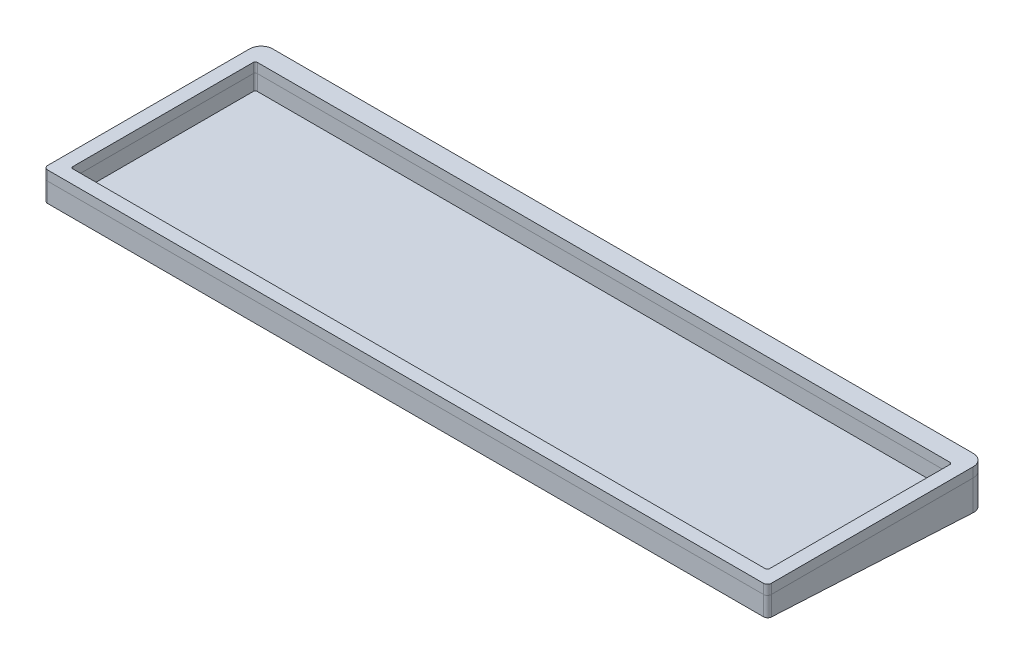
SolidWorks part; units mm, degrees
ref_plane "Front Plane" through (0, 0, 0) normal (0, 0, 1) x (1, 0, 0)
ref_plane "Top Plane" through (0, 0, 0) normal (0, 1, 0) x (1, 0, 0)
ref_plane "Right Plane" through (0, 0, 0) normal (1, 0, 0) x (0, 0, -1)
sketch "Sketch1" plane through (0, 0, 0) normal (0, 1, 0) x (1, 0, 0)
  line L1 (-178.825, 47.625) -> (178.825, 47.625)
  line L2 (-179.825, 46.625) -> (-179.825, -46.625)
  line L3 (-178.825, -47.625) -> (178.825, -47.625)
  line L4 (179.825, 46.625) -> (179.825, -46.625)
  line L5 (-179.825, 47.625) -> (179.825, -47.625) construction
  line L6 (-179.825, -47.625) -> (179.825, 47.625) construction
  arc A0 (178.825, -47.625) -> (179.825, -46.625) centre (178.825, -46.625) ccw
  arc A1 (178.825, 47.625) -> (179.825, 46.625) centre (178.825, 46.625) cw
  arc A2 (-179.825, -46.625) -> (-178.825, -47.625) centre (-178.825, -46.625) ccw
  arc A3 (-178.825, 47.625) -> (-179.825, 46.625) centre (-178.825, 46.625) ccw
  circle A4 centre (157.075, 19.175) radius 1.1
  circle A5 centre (136.925, -16.775) radius 1.1
  circle A6 centre (-153.475, 33.725) radius 1.1
  circle A7 centre (17.925, 22.275) radius 1.1
  circle A8 centre (17.875, -35.075) radius 1.1
  circle A9 centre (-130.375, -35.725) radius 1.1
  point P0 (0, 0)
  dimension "D3" = 1
  dimension "D4" = 2.2
  dimension "D7" = 2.2
  dimension "D8" = 2.2
  dimension "D9" = 2.2
  dimension "D10" = 2.2
  dimension "D11" = 2.2
  dimension "D1" = 359.65
  dimension "D2" = 95.25
  dimension "D5" = 22.75
  dimension "D6" = 28.45
  dimension "D12" = 42.9
  dimension "D13" = 30.85
  dimension "D14" = 25.35
  dimension "D15" = 161.9
  dimension "D16" = 12.55
  dimension "D17" = 161.95
  dimension "D18" = 11.9
  dimension "D19" = 49.45
  dimension "D20" = 13.9
  dimension "D21" = 26.35
sketch "Sketch2" plane through (0, 0, 0) normal (0, 1, 0) x (1, 0, 0)
  line L0 (-179.825, 46.625) -> (-179.825, -46.625) construction
  line L1 (-178.825, -47.625) -> (178.825, -47.625) construction
  line L2 (179.825, 46.625) -> (179.825, -46.625) construction
  line L3 (-178.825, 47.625) -> (178.825, 47.625) construction
  line L4 (-179.825, 46.625) -> (-179.825, -46.625)
  line L5 (-178.825, -47.625) -> (178.825, -47.625)
  line L6 (179.825, 46.625) -> (179.825, -46.625)
  line L7 (-178.825, 47.625) -> (178.825, 47.625)
  line L9 (-180.825, 57.625) -> (180.825, 57.625)
  line L10 (-186.825, 51.625) -> (-186.825, -52.625)
  line L11 (-184.825, -54.625) -> (184.825, -54.625)
  line L12 (186.825, 51.625) -> (186.825, -52.625)
  circle A0 centre (157.075, 19.175) radius 1.1 construction
  circle A1 centre (136.925, -16.775) radius 1.1 construction
  circle A2 centre (17.875, -35.075) radius 1.1 construction
  circle A3 centre (17.925, 22.275) radius 1.1 construction
  circle A4 centre (-153.475, 33.725) radius 1.1 construction
  circle A5 centre (-130.375, -35.725) radius 1.1 construction
  arc A6 (-179.825, -46.625) -> (-178.825, -47.625) centre (-178.825, -46.625) ccw construction
  arc A7 (178.825, -47.625) -> (179.825, -46.625) centre (178.825, -46.625) ccw construction
  arc A8 (179.825, 46.625) -> (178.825, 47.625) centre (178.825, 46.625) ccw construction
  arc A9 (-178.825, 47.625) -> (-179.825, 46.625) centre (-178.825, 46.625) ccw construction
  circle A10 centre (157.075, 19.175) radius 1.1
  circle A11 centre (136.925, -16.775) radius 1.1
  circle A12 centre (17.875, -35.075) radius 1.1
  circle A13 centre (17.925, 22.275) radius 1.1
  circle A14 centre (-153.475, 33.725) radius 1.1
  circle A15 centre (-130.375, -35.725) radius 1.1
  arc A16 (-179.825, -46.625) -> (-178.825, -47.625) centre (-178.825, -46.625) ccw
  arc A17 (178.825, -47.625) -> (179.825, -46.625) centre (178.825, -46.625) ccw
  arc A18 (179.825, 46.625) -> (178.825, 47.625) centre (178.825, 46.625) ccw
  arc A19 (-178.825, 47.625) -> (-179.825, 46.625) centre (-178.825, 46.625) ccw
  arc A20 (180.825, 57.625) -> (186.825, 51.625) centre (180.825, 51.625) cw
  arc A21 (-180.825, 57.625) -> (-186.825, 51.625) centre (-180.825, 51.625) ccw
  arc A22 (184.825, -54.625) -> (186.825, -52.625) centre (184.825, -52.625) ccw
  arc A23 (-186.825, -52.625) -> (-184.825, -54.625) centre (-184.825, -52.625) ccw
  point P30 (0, 0)
  dimension "D5" = 6
  dimension "D6" = 2
  dimension "D1" = 10
  dimension "D2" = 7
  dimension "D3" = 7
  dimension "D4" = 7
extrude "Boss-Extrude1" add sketch "Sketch2" along normal blind 13 contours L10 A23 L11 A22 L12 A20 L9 A21 A19 L7 A18 L6 A17 L5 A16 L4 region at (0, 0, -53.7235)
sketch "Sketch4" plane through (0, 0, 0) normal (0, -1, 0) x (1, 0, 0)
  line L0 (186.825, -51.625) -> (186.825, 52.625) construction
  line L1 (-180.825, -57.625) -> (180.825, -57.625) construction
  line L2 (-186.825, -51.625) -> (-186.825, 52.625) construction
  line L3 (-184.825, 54.625) -> (184.825, 54.625) construction
  line L4 (-179.825, 46.625) -> (-179.825, -46.625)
  line L5 (178.825, 47.625) -> (-178.825, 47.625)
  line L6 (179.825, -46.625) -> (179.825, 46.625)
  line L7 (-178.825, -47.625) -> (178.825, -47.625)
  line L8 (-179.825, 46.625) -> (-179.825, -46.625)
  line L10 (179.825, -46.625) -> (179.825, 46.625)
  line L11 (-178.825, -47.625) -> (178.825, -47.625)
  line L12 (186.825, -51.625) -> (186.825, 52.625)
  line L13 (-180.825, -57.625) -> (180.825, -57.625)
  line L14 (-186.825, -51.625) -> (-186.825, 52.625)
  line L15 (-184.825, 54.625) -> (184.825, 54.625)
  arc A0 (186.825, 52.625) -> (184.825, 54.625) centre (184.825, 52.625) ccw construction
  arc A1 (180.825, -57.625) -> (186.825, -51.625) centre (180.825, -51.625) ccw construction
  arc A2 (-186.825, -51.625) -> (-180.825, -57.625) centre (-180.825, -51.625) ccw construction
  arc A3 (-184.825, 54.625) -> (-186.825, 52.625) centre (-184.825, 52.625) ccw construction
  arc A4 (-179.825, -46.625) -> (-178.825, -47.625) centre (-178.825, -46.625) ccw
  arc A5 (-178.825, 47.625) -> (-179.825, 46.625) centre (-178.825, 46.625) ccw
  arc A6 (179.825, 46.625) -> (178.825, 47.625) centre (178.825, 46.625) ccw
  arc A7 (178.825, -47.625) -> (179.825, -46.625) centre (178.825, -46.625) ccw
  arc A8 (-179.825, -46.625) -> (-178.825, -47.625) centre (-178.825, -46.625) ccw
  arc A9 (-178.825, 47.625) -> (-179.825, 46.625) centre (-178.825, 46.625) ccw
  arc A10 (179.825, 46.625) -> (178.825, 47.625) centre (178.825, 46.625) ccw
  arc A11 (178.825, -47.625) -> (179.825, -46.625) centre (178.825, -46.625) ccw
  arc A12 (186.825, 52.625) -> (184.825, 54.625) centre (184.825, 52.625) ccw
  arc A13 (180.825, -57.625) -> (186.825, -51.625) centre (180.825, -51.625) ccw
  arc A14 (-186.825, -51.625) -> (-180.825, -57.625) centre (-180.825, -51.625) ccw
  arc A15 (-184.825, 54.625) -> (-186.825, 52.625) centre (-184.825, 52.625) ccw
  arc M9 (-178.825, -47.625) -> (-179.825, -46.625) centre (-178.825, -46.625) cw
  line M10 (-179.825, -46.625) -> (-179.825, 46.625)
  arc M11 (-179.825, 46.625) -> (-178.825, 47.625) centre (-178.825, 46.625) cw
  line M12 (-178.825, 47.625) -> (178.825, 47.625)
  arc M13 (178.825, 47.625) -> (179.825, 46.625) centre (178.825, 46.625) cw
  line M14 (179.825, 46.625) -> (179.825, -46.625)
  arc M15 (179.825, -46.625) -> (178.825, -47.625) centre (178.825, -46.625) cw
  line M16 (178.825, -47.625) -> (-178.825, -47.625)
  line M17 (-186.825, 52.625) -> (-186.825, -51.625)
  arc M18 (-186.825, -51.625) -> (-180.825, -57.625) centre (-180.825, -51.625) ccw
  line M19 (-180.825, -57.625) -> (180.825, -57.625)
  arc M20 (180.825, -57.625) -> (186.825, -51.625) centre (180.825, -51.625) ccw
  line M21 (186.825, -51.625) -> (186.825, 52.625)
  arc M22 (186.825, 52.625) -> (184.825, 54.625) centre (184.825, 52.625) ccw
  line M23 (184.825, 54.625) -> (-184.825, 54.625)
  arc M24 (-184.825, 54.625) -> (-186.825, 52.625) centre (-184.825, 52.625) ccw
  dimension "D1" = 0
extrude "Boss-Extrude3" add sketch "Sketch4" along normal blind 10.5 contours M24 M17 M18 M19 M20 M21 M22 M23 M16 M9 M10 M11 M12 M13 M14 M15 | M9 M16 M15 M14 M13 M12 M11 M10 region at (0, 0, 0) region at (182.3089, 0, -53.1089)
sketch "Sketch8" plane through (-186.825, 0, 0) normal (-1, 0, 0) x (0, 0, 1)
  line L0 (54.625, 0) -> (-57.625, 0) construction
  line L2 (-57.625, 13) -> (-57.625, -10.5) construction
  line L4 (-57.625, -7.8828) -> (-57.625, -10.5)
  line L5 (-57.625, -10.5) -> (54.625, -10.5)
  line L11 (54.625, -2) -> (54.625, -10.5)
  line L12 (54.625, 13) -> (54.625, -10.5) construction
  line L13 (-57.625, -7.8828) -> (54.625, -2)
  point P3 (54.625, -1.946)
  point P10 (-57.625, -8.0998)
  dimension "D1" = 2
  dimension "D2" = 10.5
  dimension "D3" = 87
extrude "Cut-Extrude4" cut sketch "Sketch8" against normal blind 400
sketch "Sketch9" plane through (0, 0, 0) normal (0, 1, 0) x (1, 0, 0)
  line L0 (-121.9453, 45.1) -> (-108.9453, 45.1)
  line L1 (-121.9453, 31.1) -> (-108.9453, 31.1)
  line L2 (-122.4453, 44.6) -> (-122.4453, 31.6)
  line L3 (-108.4453, 44.6) -> (-108.4453, 31.6)
  line L4 (-102.8953, 45.1) -> (-89.8953, 45.1)
  line L5 (-102.8953, 31.1) -> (-89.8953, 31.1)
  line L6 (-103.3953, 44.6) -> (-103.3953, 31.6)
  line L7 (-89.3953, 44.6) -> (-89.3953, 31.6)
  line L8 (-83.8453, 45.1) -> (-70.8453, 45.1)
  line L9 (-83.8453, 31.1) -> (-70.8453, 31.1)
  line L10 (-84.3453, 44.6) -> (-84.3453, 31.6)
  line L11 (-70.3453, 44.6) -> (-70.3453, 31.6)
  line L12 (-64.7953, 45.1) -> (-51.7953, 45.1)
  line L13 (-64.7953, 31.1) -> (-51.7953, 31.1)
  line L14 (-65.2953, 44.6) -> (-65.2953, 31.6)
  line L15 (-51.2953, 44.6) -> (-51.2953, 31.6)
  line L16 (-45.7453, 45.1) -> (-32.7453, 45.1)
  line L17 (-45.7453, 31.1) -> (-32.7453, 31.1)
  line L18 (-46.2453, 44.6) -> (-46.2453, 31.6)
  line L19 (-32.2453, 44.6) -> (-32.2453, 31.6)
  line L20 (-26.6953, 45.1) -> (-13.6953, 45.1)
  line L21 (-26.6953, 31.1) -> (-13.6953, 31.1)
  line L22 (-27.1953, 44.6) -> (-27.1953, 31.6)
  line L23 (-13.1953, 44.6) -> (-13.1953, 31.6)
  line L24 (-7.6453, 45.1) -> (5.3547, 45.1)
  line L25 (-7.6453, 31.1) -> (5.3547, 31.1)
  line L26 (-8.1453, 44.6) -> (-8.1453, 31.6)
  line L27 (5.8547, 44.6) -> (5.8547, 31.6)
  line L28 (11.4047, 45.1) -> (24.4047, 45.1)
  line L29 (11.4047, 31.1) -> (24.4047, 31.1)
  line L30 (10.9047, 44.6) -> (10.9047, 31.6)
  line L31 (24.9047, 44.6) -> (24.9047, 31.6)
  line L32 (30.4547, 45.1) -> (43.4547, 45.1)
  line L33 (30.4547, 31.1) -> (43.4547, 31.1)
  line L34 (29.9547, 44.6) -> (29.9547, 31.6)
  line L35 (43.9547, 44.6) -> (43.9547, 31.6)
  line L36 (49.5047, 45.1) -> (62.5047, 45.1)
  line L37 (49.5047, 31.1) -> (62.5047, 31.1)
  line L38 (49.0047, 44.6) -> (49.0047, 31.6)
  line L39 (63.0047, 44.6) -> (63.0047, 31.6)
  line L40 (68.5547, 45.1) -> (81.5547, 45.1)
  line L41 (68.5547, 31.1) -> (81.5547, 31.1)
  line L42 (68.0547, 44.6) -> (68.0547, 31.6)
  line L43 (82.0547, 44.6) -> (82.0547, 31.6)
  line L44 (87.6047, 45.1) -> (100.6047, 45.1)
  line L45 (87.6047, 31.1) -> (100.6047, 31.1)
  line L46 (87.1047, 44.6) -> (87.1047, 31.6)
  line L47 (101.1047, 44.6) -> (101.1047, 31.6)
  line L48 (106.6547, 45.1) -> (119.6547, 45.1)
  line L49 (106.6547, 31.1) -> (119.6547, 31.1)
  line L50 (106.1547, 44.6) -> (106.1547, 31.6)
  line L51 (120.1547, 44.6) -> (120.1547, 31.6)
  line L52 (135.2297, 45.1) -> (148.2297, 45.1)
  line L53 (135.2297, 31.1) -> (148.2297, 31.1)
  line L54 (134.7297, 44.6) -> (134.7297, 31.6)
  line L55 (148.7297, 44.6) -> (148.7297, 31.6)
  line L56 (150.6677, 44.1) -> (156.6677, 44.1)
  line L57 (150.6677, 29.1) -> (156.6677, 29.1)
  line L58 (150.1677, 43.6) -> (150.1677, 29.6)
  line L59 (157.1677, 43.6) -> (157.1677, 29.6)
  line L60 (126.7917, 44.1) -> (132.7917, 44.1)
  line L61 (126.7917, 29.1) -> (132.7917, 29.1)
  line L62 (126.2917, 43.6) -> (126.2917, 29.6)
  line L63 (133.2917, 43.6) -> (133.2917, 29.6)
  line L64 (163.8047, 45.1) -> (176.8047, 45.1)
  line L65 (163.8047, 31.1) -> (176.8047, 31.1)
  line L66 (163.3047, 44.6) -> (163.3047, 31.6)
  line L67 (177.3047, 44.6) -> (177.3047, 31.6)
  line L68 (-117.1828, 26.05) -> (-104.1828, 26.05)
  line L69 (-117.1828, 12.05) -> (-104.1828, 12.05)
  line L70 (-117.6828, 25.55) -> (-117.6828, 12.55)
  line L71 (-103.6828, 25.55) -> (-103.6828, 12.55)
  line L72 (-93.3703, 26.05) -> (-80.3703, 26.05)
  line L73 (-93.3703, 12.05) -> (-80.3703, 12.05)
  line L74 (-93.8703, 25.55) -> (-93.8703, 12.55)
  line L75 (-79.8703, 25.55) -> (-79.8703, 12.55)
  line L76 (-74.3203, 26.05) -> (-61.3203, 26.05)
  line L77 (-74.3203, 12.05) -> (-61.3203, 12.05)
  line L78 (-74.8203, 25.55) -> (-74.8203, 12.55)
  line L79 (-60.8203, 25.55) -> (-60.8203, 12.55)
  line L80 (-55.2703, 26.05) -> (-42.2703, 26.05)
  line L81 (-55.2703, 12.05) -> (-42.2703, 12.05)
  line L82 (-55.7703, 25.55) -> (-55.7703, 12.55)
  line L83 (-41.7703, 25.55) -> (-41.7703, 12.55)
  line L84 (-36.2203, 26.05) -> (-23.2203, 26.05)
  line L85 (-36.2203, 12.05) -> (-23.2203, 12.05)
  line L86 (-36.7203, 25.55) -> (-36.7203, 12.55)
  line L87 (-22.7203, 25.55) -> (-22.7203, 12.55)
  line L88 (-17.1703, 26.05) -> (-4.1703, 26.05)
  line L89 (-17.1703, 12.05) -> (-4.1703, 12.05)
  line L90 (-17.6703, 25.55) -> (-17.6703, 12.55)
  line L91 (-3.6703, 25.55) -> (-3.6703, 12.55)
  line L92 (1.8797, 26.05) -> (14.8797, 26.05)
  line L93 (1.8797, 12.05) -> (14.8797, 12.05)
  line L94 (1.3797, 25.55) -> (1.3797, 12.55)
  line L95 (15.3797, 25.55) -> (15.3797, 12.55)
  line L96 (20.9297, 26.05) -> (33.9297, 26.05)
  line L97 (20.9297, 12.05) -> (33.9297, 12.05)
  line L98 (20.4297, 25.55) -> (20.4297, 12.55)
  line L99 (34.4297, 25.55) -> (34.4297, 12.55)
  line L100 (39.9797, 26.05) -> (52.9797, 26.05)
  line L101 (39.9797, 12.05) -> (52.9797, 12.05)
  line L102 (39.4797, 25.55) -> (39.4797, 12.55)
  line L103 (53.4797, 25.55) -> (53.4797, 12.55)
  line L104 (59.0297, 26.05) -> (72.0297, 26.05)
  line L105 (59.0297, 12.05) -> (72.0297, 12.05)
  line L106 (58.5297, 25.55) -> (58.5297, 12.55)
  line L107 (72.5297, 25.55) -> (72.5297, 12.55)
  line L108 (78.0797, 26.05) -> (91.0797, 26.05)
  line L109 (78.0797, 12.05) -> (91.0797, 12.05)
  line L110 (77.5797, 25.55) -> (77.5797, 12.55)
  line L111 (91.5797, 25.55) -> (91.5797, 12.55)
  line L112 (97.1297, 26.05) -> (110.1297, 26.05)
  line L113 (97.1297, 12.05) -> (110.1297, 12.05)
  line L114 (96.6297, 25.55) -> (96.6297, 12.55)
  line L115 (110.6297, 25.55) -> (110.6297, 12.55)
  line L116 (116.1797, 26.05) -> (129.1797, 26.05)
  line L117 (116.1797, 12.05) -> (129.1797, 12.05)
  line L118 (115.6797, 25.55) -> (115.6797, 12.55)
  line L119 (129.6797, 25.55) -> (129.6797, 12.55)
  line L120 (139.9922, 26.05) -> (152.9922, 26.05)
  line L121 (139.9922, 12.05) -> (152.9922, 12.05)
  line L122 (139.4922, 25.55) -> (139.4922, 12.55)
  line L123 (153.4922, 25.55) -> (153.4922, 12.55)
  line L124 (163.8047, 26.05) -> (176.8047, 26.05)
  line L125 (163.8047, 12.05) -> (176.8047, 12.05)
  line L126 (163.3047, 25.55) -> (163.3047, 12.55)
  line L127 (177.3047, 25.55) -> (177.3047, 12.55)
  line L128 (-114.8016, 7) -> (-101.8016, 7)
  line L129 (-114.8016, -7) -> (-101.8016, -7)
  line L130 (-115.3016, 6.5) -> (-115.3016, -6.5)
  line L131 (-101.3016, 6.5) -> (-101.3016, -6.5)
  line L132 (-88.6078, 7) -> (-75.6078, 7)
  line L133 (-88.6078, -7) -> (-75.6078, -7)
  line L134 (-89.1078, 6.5) -> (-89.1078, -6.5)
  line L135 (-75.1078, 6.5) -> (-75.1078, -6.5)
  line L136 (-69.5578, 7) -> (-56.5578, 7)
  line L137 (-69.5578, -7) -> (-56.5578, -7)
  line L138 (-70.0578, 6.5) -> (-70.0578, -6.5)
  line L139 (-56.0578, 6.5) -> (-56.0578, -6.5)
  line L140 (-50.5078, 7) -> (-37.5078, 7)
  line L141 (-50.5078, -7) -> (-37.5078, -7)
  line L142 (-51.0078, 6.5) -> (-51.0078, -6.5)
  line L143 (-37.0078, 6.5) -> (-37.0078, -6.5)
  line L144 (-31.4578, 7) -> (-18.4578, 7)
  line L145 (-31.4578, -7) -> (-18.4578, -7)
  line L146 (-31.9578, 6.5) -> (-31.9578, -6.5)
  line L147 (-17.9578, 6.5) -> (-17.9578, -6.5)
  line L148 (-12.4078, 7) -> (0.5922, 7)
  line L149 (-12.4078, -7) -> (0.5922, -7)
  line L150 (-12.9078, 6.5) -> (-12.9078, -6.5)
  line L151 (1.0922, 6.5) -> (1.0922, -6.5)
  line L152 (6.6422, 7) -> (19.6422, 7)
  line L153 (6.6422, -7) -> (19.6422, -7)
  line L154 (6.1422, 6.5) -> (6.1422, -6.5)
  line L155 (20.1422, 6.5) -> (20.1422, -6.5)
  line L156 (25.6922, 7) -> (38.6922, 7)
  line L157 (25.6922, -7) -> (38.6922, -7)
  line L158 (25.1922, 6.5) -> (25.1922, -6.5)
  line L159 (39.1922, 6.5) -> (39.1922, -6.5)
  line L160 (44.7422, 7) -> (57.7422, 7)
  line L161 (44.7422, -7) -> (57.7422, -7)
  line L162 (44.2422, 6.5) -> (44.2422, -6.5)
  line L163 (58.2422, 6.5) -> (58.2422, -6.5)
  line L164 (63.7922, 7) -> (76.7922, 7)
  line L165 (63.7922, -7) -> (76.7922, -7)
  line L166 (63.2922, 6.5) -> (63.2922, -6.5)
  line L167 (77.2922, 6.5) -> (77.2922, -6.5)
  line L168 (82.8422, 7) -> (95.8422, 7)
  line L169 (82.8422, -7) -> (95.8422, -7)
  line L170 (82.3422, 6.5) -> (82.3422, -6.5)
  line L171 (96.3422, 6.5) -> (96.3422, -6.5)
  line L172 (101.8922, 7) -> (114.8922, 7)
  line L173 (101.8922, -7) -> (114.8922, -7)
  line L174 (101.3922, 6.5) -> (101.3922, -6.5)
  line L175 (115.3922, 6.5) -> (115.3922, -6.5)
  line L176 (132.8484, 7) -> (145.8484, 7)
  line L177 (132.8484, -7) -> (145.8484, -7)
  line L178 (132.3484, 6.5) -> (132.3484, -6.5)
  line L179 (146.3484, 6.5) -> (146.3484, -6.5)
  line L180 (148.2864, 6) -> (154.2864, 6)
  line L181 (148.2864, -9) -> (154.2864, -9)
  line L182 (147.7864, 5.5) -> (147.7864, -8.5)
  line L183 (154.7864, 5.5) -> (154.7864, -8.5)
  line L184 (124.4104, 6) -> (130.4104, 6)
  line L185 (124.4104, -9) -> (130.4104, -9)
  line L186 (123.9104, 5.5) -> (123.9104, -8.5)
  line L187 (130.9104, 5.5) -> (130.9104, -8.5)
  line L188 (163.8047, 7) -> (176.8047, 7)
  line L189 (163.8047, -7) -> (176.8047, -7)
  line L190 (163.3047, 6.5) -> (163.3047, -6.5)
  line L191 (177.3047, 6.5) -> (177.3047, -6.5)
  line L192 (-110.0391, -12.05) -> (-97.0391, -12.05)
  line L193 (-110.0391, -26.05) -> (-97.0391, -26.05)
  line L194 (-110.5391, -12.55) -> (-110.5391, -25.55)
  line L195 (-96.5391, -12.55) -> (-96.5391, -25.55)
  line L196 (-94.6011, -13.05) -> (-88.6011, -13.05)
  line L197 (-94.6011, -28.05) -> (-88.6011, -28.05)
  line L198 (-95.1011, -13.55) -> (-95.1011, -27.55)
  line L199 (-88.1011, -13.55) -> (-88.1011, -27.55)
  line L200 (-118.4771, -13.05) -> (-112.4771, -13.05)
  line L201 (-118.4771, -28.05) -> (-112.4771, -28.05)
  line L202 (-118.9771, -13.55) -> (-118.9771, -27.55)
  line L203 (-111.9771, -13.55) -> (-111.9771, -27.55)
  line L204 (-79.0828, -12.05) -> (-66.0828, -12.05)
  line L205 (-79.0828, -26.05) -> (-66.0828, -26.05)
  line L206 (-79.5828, -12.55) -> (-79.5828, -25.55)
  line L207 (-65.5828, -12.55) -> (-65.5828, -25.55)
  line L208 (-60.0328, -12.05) -> (-47.0328, -12.05)
  line L209 (-60.0328, -26.05) -> (-47.0328, -26.05)
  line L210 (-60.5328, -12.55) -> (-60.5328, -25.55)
  line L211 (-46.5328, -12.55) -> (-46.5328, -25.55)
  line L212 (-40.9828, -12.05) -> (-27.9828, -12.05)
  line L213 (-40.9828, -26.05) -> (-27.9828, -26.05)
  line L214 (-41.4828, -12.55) -> (-41.4828, -25.55)
  line L215 (-27.4828, -12.55) -> (-27.4828, -25.55)
  line L216 (-21.9328, -12.05) -> (-8.9328, -12.05)
  line L217 (-21.9328, -26.05) -> (-8.9328, -26.05)
  line L218 (-22.4328, -12.55) -> (-22.4328, -25.55)
  line L219 (-8.4328, -12.55) -> (-8.4328, -25.55)
  line L220 (-2.8828, -12.05) -> (10.1172, -12.05)
  line L221 (-2.8828, -26.05) -> (10.1172, -26.05)
  line L222 (-3.3828, -12.55) -> (-3.3828, -25.55)
  line L223 (10.6172, -12.55) -> (10.6172, -25.55)
  line L224 (16.1672, -12.05) -> (29.1672, -12.05)
  line L225 (16.1672, -26.05) -> (29.1672, -26.05)
  line L226 (15.6672, -12.55) -> (15.6672, -25.55)
  line L227 (29.6672, -12.55) -> (29.6672, -25.55)
  line L228 (35.2172, -12.05) -> (48.2172, -12.05)
  line L229 (35.2172, -26.05) -> (48.2172, -26.05)
  line L230 (34.7172, -12.55) -> (34.7172, -25.55)
  line L231 (48.7172, -12.55) -> (48.7172, -25.55)
  line L232 (54.2672, -12.05) -> (67.2672, -12.05)
  line L233 (54.2672, -26.05) -> (67.2672, -26.05)
  line L234 (53.7672, -12.55) -> (53.7672, -25.55)
  line L235 (67.7672, -12.55) -> (67.7672, -25.55)
  line L236 (73.3172, -12.05) -> (86.3172, -12.05)
  line L237 (73.3172, -26.05) -> (86.3172, -26.05)
  line L238 (72.8172, -12.55) -> (72.8172, -25.55)
  line L239 (86.8172, -12.55) -> (86.8172, -25.55)
  line L240 (92.3672, -12.05) -> (105.3672, -12.05)
  line L241 (92.3672, -26.05) -> (105.3672, -26.05)
  line L242 (91.8672, -12.55) -> (91.8672, -25.55)
  line L243 (105.8672, -12.55) -> (105.8672, -25.55)
  line L244 (118.5609, -12.05) -> (131.5609, -12.05)
  line L245 (118.5609, -26.05) -> (131.5609, -26.05)
  line L246 (118.0609, -12.55) -> (118.0609, -25.55)
  line L247 (132.0609, -12.55) -> (132.0609, -25.55)
  line L248 (144.7547, -12.05) -> (157.7547, -12.05)
  line L249 (144.7547, -26.05) -> (157.7547, -26.05)
  line L250 (144.2547, -12.55) -> (144.2547, -25.55)
  line L251 (158.2547, -12.55) -> (158.2547, -25.55)
  line L252 (163.8047, -12.05) -> (176.8047, -12.05)
  line L253 (163.8047, -26.05) -> (176.8047, -26.05)
  line L254 (163.3047, -12.55) -> (163.3047, -25.55)
  line L255 (177.3047, -12.55) -> (177.3047, -25.55)
  line L256 (-119.5641, -31.1) -> (-106.5641, -31.1)
  line L257 (-119.5641, -45.1) -> (-106.5641, -45.1)
  line L258 (-120.0641, -31.6) -> (-120.0641, -44.6)
  line L259 (-106.0641, -31.6) -> (-106.0641, -44.6)
  line L260 (-95.7516, -31.1) -> (-82.7516, -31.1)
  line L261 (-95.7516, -45.1) -> (-82.7516, -45.1)
  line L262 (-96.2516, -31.6) -> (-96.2516, -44.6)
  line L263 (-82.2516, -31.6) -> (-82.2516, -44.6)
  line L264 (-71.9391, -31.1) -> (-58.9391, -31.1)
  line L265 (-71.9391, -45.1) -> (-58.9391, -45.1)
  line L266 (-72.4391, -31.6) -> (-72.4391, -44.6)
  line L267 (-58.4391, -31.6) -> (-58.4391, -44.6)
  line L268 (-0.5016, -31.1) -> (12.4984, -31.1)
  line L269 (-0.5016, -45.1) -> (12.4984, -45.1)
  line L270 (-1.0016, -31.6) -> (-1.0016, -44.6)
  line L271 (12.9984, -31.6) -> (12.9984, -44.6)
  line L272 (52.9984, -32.1) -> (58.9984, -32.1)
  line L273 (52.9984, -47.1) -> (58.9984, -47.1)
  line L274 (52.4984, -32.6) -> (52.4984, -46.6)
  line L275 (59.4984, -32.6) -> (59.4984, -46.6)
  line L276 (-47.0016, -32.1) -> (-41.0016, -32.1)
  line L277 (-47.0016, -47.1) -> (-41.0016, -47.1)
  line L278 (-47.5016, -32.6) -> (-47.5016, -46.6)
  line L279 (-40.5016, -32.6) -> (-40.5016, -46.6)
  line L280 (68.5547, -31.1) -> (81.5547, -31.1)
  line L281 (68.5547, -45.1) -> (81.5547, -45.1)
  line L282 (68.0547, -31.6) -> (68.0547, -44.6)
  line L283 (82.0547, -31.6) -> (82.0547, -44.6)
  line L284 (87.6047, -31.1) -> (100.6047, -31.1)
  line L285 (87.6047, -45.1) -> (100.6047, -45.1)
  line L286 (87.1047, -31.6) -> (87.1047, -44.6)
  line L287 (101.1047, -31.6) -> (101.1047, -44.6)
  line L288 (106.6547, -31.1) -> (119.6547, -31.1)
  line L289 (106.6547, -45.1) -> (119.6547, -45.1)
  line L290 (106.1547, -31.6) -> (106.1547, -44.6)
  line L291 (120.1547, -31.6) -> (120.1547, -44.6)
  line L292 (125.7047, -31.1) -> (138.7047, -31.1)
  line L293 (125.7047, -45.1) -> (138.7047, -45.1)
  line L294 (125.2047, -31.6) -> (125.2047, -44.6)
  line L295 (139.2047, -31.6) -> (139.2047, -44.6)
  line L296 (144.7547, -31.1) -> (157.7547, -31.1)
  line L297 (144.7547, -45.1) -> (157.7547, -45.1)
  line L298 (144.2547, -31.6) -> (144.2547, -44.6)
  line L299 (158.2547, -31.6) -> (158.2547, -44.6)
  line L300 (163.8047, -31.1) -> (176.8047, -31.1)
  line L301 (163.8047, -45.1) -> (176.8047, -45.1)
  line L302 (163.3047, -31.6) -> (163.3047, -44.6)
  line L303 (177.3047, -31.6) -> (177.3047, -44.6)
  line L304 (-124.9703, 47.625) -> (179.8297, 47.625)
  line L305 (-124.9703, -47.625) -> (179.8297, -47.625)
  line L306 (-124.9703, 47.625) -> (-124.9703, -47.625)
  line L307 (179.8297, 47.625) -> (179.8297, -47.625)
  arc A0 (-121.9453, 45.1) -> (-122.4453, 44.6) centre (-121.9453, 44.6) ccw
  arc A1 (-108.4453, 44.6) -> (-108.9453, 45.1) centre (-108.9453, 44.6) ccw
  arc A2 (-122.4453, 31.6) -> (-121.9453, 31.1) centre (-121.9453, 31.6) ccw
  arc A3 (-108.9453, 31.1) -> (-108.4453, 31.6) centre (-108.9453, 31.6) ccw
  arc A4 (-102.8953, 45.1) -> (-103.3953, 44.6) centre (-102.8953, 44.6) ccw
  arc A5 (-89.3953, 44.6) -> (-89.8953, 45.1) centre (-89.8953, 44.6) ccw
  arc A6 (-103.3953, 31.6) -> (-102.8953, 31.1) centre (-102.8953, 31.6) ccw
  arc A7 (-89.8953, 31.1) -> (-89.3953, 31.6) centre (-89.8953, 31.6) ccw
  arc A8 (-83.8453, 45.1) -> (-84.3453, 44.6) centre (-83.8453, 44.6) ccw
  arc A9 (-70.3453, 44.6) -> (-70.8453, 45.1) centre (-70.8453, 44.6) ccw
  arc A10 (-84.3453, 31.6) -> (-83.8453, 31.1) centre (-83.8453, 31.6) ccw
  arc A11 (-70.8453, 31.1) -> (-70.3453, 31.6) centre (-70.8453, 31.6) ccw
  arc A12 (-64.7953, 45.1) -> (-65.2953, 44.6) centre (-64.7953, 44.6) ccw
  arc A13 (-51.2953, 44.6) -> (-51.7953, 45.1) centre (-51.7953, 44.6) ccw
  arc A14 (-65.2953, 31.6) -> (-64.7953, 31.1) centre (-64.7953, 31.6) ccw
  arc A15 (-51.7953, 31.1) -> (-51.2953, 31.6) centre (-51.7953, 31.6) ccw
  arc A16 (-45.7453, 45.1) -> (-46.2453, 44.6) centre (-45.7453, 44.6) ccw
  arc A17 (-32.2453, 44.6) -> (-32.7453, 45.1) centre (-32.7453, 44.6) ccw
  arc A18 (-46.2453, 31.6) -> (-45.7453, 31.1) centre (-45.7453, 31.6) ccw
  arc A19 (-32.7453, 31.1) -> (-32.2453, 31.6) centre (-32.7453, 31.6) ccw
  arc A20 (-26.6953, 45.1) -> (-27.1953, 44.6) centre (-26.6953, 44.6) ccw
  arc A21 (-13.1953, 44.6) -> (-13.6953, 45.1) centre (-13.6953, 44.6) ccw
  arc A22 (-27.1953, 31.6) -> (-26.6953, 31.1) centre (-26.6953, 31.6) ccw
  arc A23 (-13.6953, 31.1) -> (-13.1953, 31.6) centre (-13.6953, 31.6) ccw
  arc A24 (-7.6453, 45.1) -> (-8.1453, 44.6) centre (-7.6453, 44.6) ccw
  arc A25 (5.8547, 44.6) -> (5.3547, 45.1) centre (5.3547, 44.6) ccw
  arc A26 (-8.1453, 31.6) -> (-7.6453, 31.1) centre (-7.6453, 31.6) ccw
  arc A27 (5.3547, 31.1) -> (5.8547, 31.6) centre (5.3547, 31.6) ccw
  arc A28 (11.4047, 45.1) -> (10.9047, 44.6) centre (11.4047, 44.6) ccw
  arc A29 (24.9047, 44.6) -> (24.4047, 45.1) centre (24.4047, 44.6) ccw
  arc A30 (10.9047, 31.6) -> (11.4047, 31.1) centre (11.4047, 31.6) ccw
  arc A31 (24.4047, 31.1) -> (24.9047, 31.6) centre (24.4047, 31.6) ccw
  arc A32 (30.4547, 45.1) -> (29.9547, 44.6) centre (30.4547, 44.6) ccw
  arc A33 (43.9547, 44.6) -> (43.4547, 45.1) centre (43.4547, 44.6) ccw
  arc A34 (29.9547, 31.6) -> (30.4547, 31.1) centre (30.4547, 31.6) ccw
  arc A35 (43.4547, 31.1) -> (43.9547, 31.6) centre (43.4547, 31.6) ccw
  arc A36 (49.5047, 45.1) -> (49.0047, 44.6) centre (49.5047, 44.6) ccw
  arc A37 (63.0047, 44.6) -> (62.5047, 45.1) centre (62.5047, 44.6) ccw
  arc A38 (49.0047, 31.6) -> (49.5047, 31.1) centre (49.5047, 31.6) ccw
  arc A39 (62.5047, 31.1) -> (63.0047, 31.6) centre (62.5047, 31.6) ccw
  arc A40 (68.5547, 45.1) -> (68.0547, 44.6) centre (68.5547, 44.6) ccw
  arc A41 (82.0547, 44.6) -> (81.5547, 45.1) centre (81.5547, 44.6) ccw
  arc A42 (68.0547, 31.6) -> (68.5547, 31.1) centre (68.5547, 31.6) ccw
  arc A43 (81.5547, 31.1) -> (82.0547, 31.6) centre (81.5547, 31.6) ccw
  arc A44 (87.6047, 45.1) -> (87.1047, 44.6) centre (87.6047, 44.6) ccw
  arc A45 (101.1047, 44.6) -> (100.6047, 45.1) centre (100.6047, 44.6) ccw
  arc A46 (87.1047, 31.6) -> (87.6047, 31.1) centre (87.6047, 31.6) ccw
  arc A47 (100.6047, 31.1) -> (101.1047, 31.6) centre (100.6047, 31.6) ccw
  arc A48 (106.6547, 45.1) -> (106.1547, 44.6) centre (106.6547, 44.6) ccw
  arc A49 (120.1547, 44.6) -> (119.6547, 45.1) centre (119.6547, 44.6) ccw
  arc A50 (106.1547, 31.6) -> (106.6547, 31.1) centre (106.6547, 31.6) ccw
  arc A51 (119.6547, 31.1) -> (120.1547, 31.6) centre (119.6547, 31.6) ccw
  arc A52 (135.2297, 45.1) -> (134.7297, 44.6) centre (135.2297, 44.6) ccw
  arc A53 (148.7297, 44.6) -> (148.2297, 45.1) centre (148.2297, 44.6) ccw
  arc A54 (134.7297, 31.6) -> (135.2297, 31.1) centre (135.2297, 31.6) ccw
  arc A55 (148.2297, 31.1) -> (148.7297, 31.6) centre (148.2297, 31.6) ccw
  arc A56 (150.6677, 44.1) -> (150.1677, 43.6) centre (150.6677, 43.6) ccw
  arc A57 (157.1677, 43.6) -> (156.6677, 44.1) centre (156.6677, 43.6) ccw
  arc A58 (150.1677, 29.6) -> (150.6677, 29.1) centre (150.6677, 29.6) ccw
  arc A59 (156.6677, 29.1) -> (157.1677, 29.6) centre (156.6677, 29.6) ccw
  arc A60 (126.7917, 44.1) -> (126.2917, 43.6) centre (126.7917, 43.6) ccw
  arc A61 (133.2917, 43.6) -> (132.7917, 44.1) centre (132.7917, 43.6) ccw
  arc A62 (126.2917, 29.6) -> (126.7917, 29.1) centre (126.7917, 29.6) ccw
  arc A63 (132.7917, 29.1) -> (133.2917, 29.6) centre (132.7917, 29.6) ccw
  arc A64 (163.8047, 45.1) -> (163.3047, 44.6) centre (163.8047, 44.6) ccw
  arc A65 (177.3047, 44.6) -> (176.8047, 45.1) centre (176.8047, 44.6) ccw
  arc A66 (163.3047, 31.6) -> (163.8047, 31.1) centre (163.8047, 31.6) ccw
  arc A67 (176.8047, 31.1) -> (177.3047, 31.6) centre (176.8047, 31.6) ccw
  arc A68 (-117.1828, 26.05) -> (-117.6828, 25.55) centre (-117.1828, 25.55) ccw
  arc A69 (-103.6828, 25.55) -> (-104.1828, 26.05) centre (-104.1828, 25.55) ccw
  arc A70 (-117.6828, 12.55) -> (-117.1828, 12.05) centre (-117.1828, 12.55) ccw
  arc A71 (-104.1828, 12.05) -> (-103.6828, 12.55) centre (-104.1828, 12.55) ccw
  arc A72 (-93.3703, 26.05) -> (-93.8703, 25.55) centre (-93.3703, 25.55) ccw
  arc A73 (-79.8703, 25.55) -> (-80.3703, 26.05) centre (-80.3703, 25.55) ccw
  arc A74 (-93.8703, 12.55) -> (-93.3703, 12.05) centre (-93.3703, 12.55) ccw
  arc A75 (-80.3703, 12.05) -> (-79.8703, 12.55) centre (-80.3703, 12.55) ccw
  arc A76 (-74.3203, 26.05) -> (-74.8203, 25.55) centre (-74.3203, 25.55) ccw
  arc A77 (-60.8203, 25.55) -> (-61.3203, 26.05) centre (-61.3203, 25.55) ccw
  arc A78 (-74.8203, 12.55) -> (-74.3203, 12.05) centre (-74.3203, 12.55) ccw
  arc A79 (-61.3203, 12.05) -> (-60.8203, 12.55) centre (-61.3203, 12.55) ccw
  arc A80 (-55.2703, 26.05) -> (-55.7703, 25.55) centre (-55.2703, 25.55) ccw
  arc A81 (-41.7703, 25.55) -> (-42.2703, 26.05) centre (-42.2703, 25.55) ccw
  arc A82 (-55.7703, 12.55) -> (-55.2703, 12.05) centre (-55.2703, 12.55) ccw
  arc A83 (-42.2703, 12.05) -> (-41.7703, 12.55) centre (-42.2703, 12.55) ccw
  arc A84 (-36.2203, 26.05) -> (-36.7203, 25.55) centre (-36.2203, 25.55) ccw
  arc A85 (-22.7203, 25.55) -> (-23.2203, 26.05) centre (-23.2203, 25.55) ccw
  arc A86 (-36.7203, 12.55) -> (-36.2203, 12.05) centre (-36.2203, 12.55) ccw
  arc A87 (-23.2203, 12.05) -> (-22.7203, 12.55) centre (-23.2203, 12.55) ccw
  arc A88 (-17.1703, 26.05) -> (-17.6703, 25.55) centre (-17.1703, 25.55) ccw
  arc A89 (-3.6703, 25.55) -> (-4.1703, 26.05) centre (-4.1703, 25.55) ccw
  arc A90 (-17.6703, 12.55) -> (-17.1703, 12.05) centre (-17.1703, 12.55) ccw
  arc A91 (-4.1703, 12.05) -> (-3.6703, 12.55) centre (-4.1703, 12.55) ccw
  arc A92 (1.8797, 26.05) -> (1.3797, 25.55) centre (1.8797, 25.55) ccw
  arc A93 (15.3797, 25.55) -> (14.8797, 26.05) centre (14.8797, 25.55) ccw
  arc A94 (1.3797, 12.55) -> (1.8797, 12.05) centre (1.8797, 12.55) ccw
  arc A95 (14.8797, 12.05) -> (15.3797, 12.55) centre (14.8797, 12.55) ccw
  arc A96 (20.9297, 26.05) -> (20.4297, 25.55) centre (20.9297, 25.55) ccw
  arc A97 (34.4297, 25.55) -> (33.9297, 26.05) centre (33.9297, 25.55) ccw
  arc A98 (20.4297, 12.55) -> (20.9297, 12.05) centre (20.9297, 12.55) ccw
  arc A99 (33.9297, 12.05) -> (34.4297, 12.55) centre (33.9297, 12.55) ccw
  arc A100 (39.9797, 26.05) -> (39.4797, 25.55) centre (39.9797, 25.55) ccw
  arc A101 (53.4797, 25.55) -> (52.9797, 26.05) centre (52.9797, 25.55) ccw
  arc A102 (39.4797, 12.55) -> (39.9797, 12.05) centre (39.9797, 12.55) ccw
  arc A103 (52.9797, 12.05) -> (53.4797, 12.55) centre (52.9797, 12.55) ccw
  arc A104 (59.0297, 26.05) -> (58.5297, 25.55) centre (59.0297, 25.55) ccw
  arc A105 (72.5297, 25.55) -> (72.0297, 26.05) centre (72.0297, 25.55) ccw
  arc A106 (58.5297, 12.55) -> (59.0297, 12.05) centre (59.0297, 12.55) ccw
  arc A107 (72.0297, 12.05) -> (72.5297, 12.55) centre (72.0297, 12.55) ccw
  arc A108 (78.0797, 26.05) -> (77.5797, 25.55) centre (78.0797, 25.55) ccw
  arc A109 (91.5797, 25.55) -> (91.0797, 26.05) centre (91.0797, 25.55) ccw
  arc A110 (77.5797, 12.55) -> (78.0797, 12.05) centre (78.0797, 12.55) ccw
  arc A111 (91.0797, 12.05) -> (91.5797, 12.55) centre (91.0797, 12.55) ccw
  arc A112 (97.1297, 26.05) -> (96.6297, 25.55) centre (97.1297, 25.55) ccw
  arc A113 (110.6297, 25.55) -> (110.1297, 26.05) centre (110.1297, 25.55) ccw
  arc A114 (96.6297, 12.55) -> (97.1297, 12.05) centre (97.1297, 12.55) ccw
  arc A115 (110.1297, 12.05) -> (110.6297, 12.55) centre (110.1297, 12.55) ccw
  arc A116 (116.1797, 26.05) -> (115.6797, 25.55) centre (116.1797, 25.55) ccw
  arc A117 (129.6797, 25.55) -> (129.1797, 26.05) centre (129.1797, 25.55) ccw
  arc A118 (115.6797, 12.55) -> (116.1797, 12.05) centre (116.1797, 12.55) ccw
  arc A119 (129.1797, 12.05) -> (129.6797, 12.55) centre (129.1797, 12.55) ccw
  arc A120 (139.9922, 26.05) -> (139.4922, 25.55) centre (139.9922, 25.55) ccw
  arc A121 (153.4922, 25.55) -> (152.9922, 26.05) centre (152.9922, 25.55) ccw
  arc A122 (139.4922, 12.55) -> (139.9922, 12.05) centre (139.9922, 12.55) ccw
  arc A123 (152.9922, 12.05) -> (153.4922, 12.55) centre (152.9922, 12.55) ccw
  arc A124 (163.8047, 26.05) -> (163.3047, 25.55) centre (163.8047, 25.55) ccw
  arc A125 (177.3047, 25.55) -> (176.8047, 26.05) centre (176.8047, 25.55) ccw
  arc A126 (163.3047, 12.55) -> (163.8047, 12.05) centre (163.8047, 12.55) ccw
  arc A127 (176.8047, 12.05) -> (177.3047, 12.55) centre (176.8047, 12.55) ccw
  arc A128 (-114.8016, 7) -> (-115.3016, 6.5) centre (-114.8016, 6.5) ccw
  arc A129 (-101.3016, 6.5) -> (-101.8016, 7) centre (-101.8016, 6.5) ccw
  arc A130 (-115.3016, -6.5) -> (-114.8016, -7) centre (-114.8016, -6.5) ccw
  arc A131 (-101.8016, -7) -> (-101.3016, -6.5) centre (-101.8016, -6.5) ccw
  arc A132 (-88.6078, 7) -> (-89.1078, 6.5) centre (-88.6078, 6.5) ccw
  arc A133 (-75.1078, 6.5) -> (-75.6078, 7) centre (-75.6078, 6.5) ccw
  arc A134 (-89.1078, -6.5) -> (-88.6078, -7) centre (-88.6078, -6.5) ccw
  arc A135 (-75.6078, -7) -> (-75.1078, -6.5) centre (-75.6078, -6.5) ccw
  arc A136 (-69.5578, 7) -> (-70.0578, 6.5) centre (-69.5578, 6.5) ccw
  arc A137 (-56.0578, 6.5) -> (-56.5578, 7) centre (-56.5578, 6.5) ccw
  arc A138 (-70.0578, -6.5) -> (-69.5578, -7) centre (-69.5578, -6.5) ccw
  arc A139 (-56.5578, -7) -> (-56.0578, -6.5) centre (-56.5578, -6.5) ccw
  arc A140 (-50.5078, 7) -> (-51.0078, 6.5) centre (-50.5078, 6.5) ccw
  arc A141 (-37.0078, 6.5) -> (-37.5078, 7) centre (-37.5078, 6.5) ccw
  arc A142 (-51.0078, -6.5) -> (-50.5078, -7) centre (-50.5078, -6.5) ccw
  arc A143 (-37.5078, -7) -> (-37.0078, -6.5) centre (-37.5078, -6.5) ccw
  arc A144 (-31.4578, 7) -> (-31.9578, 6.5) centre (-31.4578, 6.5) ccw
  arc A145 (-17.9578, 6.5) -> (-18.4578, 7) centre (-18.4578, 6.5) ccw
  arc A146 (-31.9578, -6.5) -> (-31.4578, -7) centre (-31.4578, -6.5) ccw
  arc A147 (-18.4578, -7) -> (-17.9578, -6.5) centre (-18.4578, -6.5) ccw
  arc A148 (-12.4078, 7) -> (-12.9078, 6.5) centre (-12.4078, 6.5) ccw
  arc A149 (1.0922, 6.5) -> (0.5922, 7) centre (0.5922, 6.5) ccw
  arc A150 (-12.9078, -6.5) -> (-12.4078, -7) centre (-12.4078, -6.5) ccw
  arc A151 (0.5922, -7) -> (1.0922, -6.5) centre (0.5922, -6.5) ccw
  arc A152 (6.6422, 7) -> (6.1422, 6.5) centre (6.6422, 6.5) ccw
  arc A153 (20.1422, 6.5) -> (19.6422, 7) centre (19.6422, 6.5) ccw
  arc A154 (6.1422, -6.5) -> (6.6422, -7) centre (6.6422, -6.5) ccw
  arc A155 (19.6422, -7) -> (20.1422, -6.5) centre (19.6422, -6.5) ccw
  arc A156 (25.6922, 7) -> (25.1922, 6.5) centre (25.6922, 6.5) ccw
  arc A157 (39.1922, 6.5) -> (38.6922, 7) centre (38.6922, 6.5) ccw
  arc A158 (25.1922, -6.5) -> (25.6922, -7) centre (25.6922, -6.5) ccw
  arc A159 (38.6922, -7) -> (39.1922, -6.5) centre (38.6922, -6.5) ccw
  arc A160 (44.7422, 7) -> (44.2422, 6.5) centre (44.7422, 6.5) ccw
  arc A161 (58.2422, 6.5) -> (57.7422, 7) centre (57.7422, 6.5) ccw
  arc A162 (44.2422, -6.5) -> (44.7422, -7) centre (44.7422, -6.5) ccw
  arc A163 (57.7422, -7) -> (58.2422, -6.5) centre (57.7422, -6.5) ccw
  arc A164 (63.7922, 7) -> (63.2922, 6.5) centre (63.7922, 6.5) ccw
  arc A165 (77.2922, 6.5) -> (76.7922, 7) centre (76.7922, 6.5) ccw
  arc A166 (63.2922, -6.5) -> (63.7922, -7) centre (63.7922, -6.5) ccw
  arc A167 (76.7922, -7) -> (77.2922, -6.5) centre (76.7922, -6.5) ccw
  arc A168 (82.8422, 7) -> (82.3422, 6.5) centre (82.8422, 6.5) ccw
  arc A169 (96.3422, 6.5) -> (95.8422, 7) centre (95.8422, 6.5) ccw
  arc A170 (82.3422, -6.5) -> (82.8422, -7) centre (82.8422, -6.5) ccw
  arc A171 (95.8422, -7) -> (96.3422, -6.5) centre (95.8422, -6.5) ccw
  arc A172 (101.8922, 7) -> (101.3922, 6.5) centre (101.8922, 6.5) ccw
  arc A173 (115.3922, 6.5) -> (114.8922, 7) centre (114.8922, 6.5) ccw
  arc A174 (101.3922, -6.5) -> (101.8922, -7) centre (101.8922, -6.5) ccw
  arc A175 (114.8922, -7) -> (115.3922, -6.5) centre (114.8922, -6.5) ccw
  arc A176 (132.8484, 7) -> (132.3484, 6.5) centre (132.8484, 6.5) ccw
  arc A177 (146.3484, 6.5) -> (145.8484, 7) centre (145.8484, 6.5) ccw
  arc A178 (132.3484, -6.5) -> (132.8484, -7) centre (132.8484, -6.5) ccw
  arc A179 (145.8484, -7) -> (146.3484, -6.5) centre (145.8484, -6.5) ccw
  arc A180 (148.2864, 6) -> (147.7864, 5.5) centre (148.2864, 5.5) ccw
  arc A181 (154.7864, 5.5) -> (154.2864, 6) centre (154.2864, 5.5) ccw
  arc A182 (147.7864, -8.5) -> (148.2864, -9) centre (148.2864, -8.5) ccw
  arc A183 (154.2864, -9) -> (154.7864, -8.5) centre (154.2864, -8.5) ccw
  arc A184 (124.4104, 6) -> (123.9104, 5.5) centre (124.4104, 5.5) ccw
  arc A185 (130.9104, 5.5) -> (130.4104, 6) centre (130.4104, 5.5) ccw
  arc A186 (123.9104, -8.5) -> (124.4104, -9) centre (124.4104, -8.5) ccw
  arc A187 (130.4104, -9) -> (130.9104, -8.5) centre (130.4104, -8.5) ccw
  arc A188 (163.8047, 7) -> (163.3047, 6.5) centre (163.8047, 6.5) ccw
  arc A189 (177.3047, 6.5) -> (176.8047, 7) centre (176.8047, 6.5) ccw
  arc A190 (163.3047, -6.5) -> (163.8047, -7) centre (163.8047, -6.5) ccw
  arc A191 (176.8047, -7) -> (177.3047, -6.5) centre (176.8047, -6.5) ccw
  arc A192 (-110.0391, -12.05) -> (-110.5391, -12.55) centre (-110.0391, -12.55) ccw
  arc A193 (-96.5391, -12.55) -> (-97.0391, -12.05) centre (-97.0391, -12.55) ccw
  arc A194 (-110.5391, -25.55) -> (-110.0391, -26.05) centre (-110.0391, -25.55) ccw
  arc A195 (-97.0391, -26.05) -> (-96.5391, -25.55) centre (-97.0391, -25.55) ccw
  arc A196 (-94.6011, -13.05) -> (-95.1011, -13.55) centre (-94.6011, -13.55) ccw
  arc A197 (-88.1011, -13.55) -> (-88.6011, -13.05) centre (-88.6011, -13.55) ccw
  arc A198 (-95.1011, -27.55) -> (-94.6011, -28.05) centre (-94.6011, -27.55) ccw
  arc A199 (-88.6011, -28.05) -> (-88.1011, -27.55) centre (-88.6011, -27.55) ccw
  arc A200 (-118.4771, -13.05) -> (-118.9771, -13.55) centre (-118.4771, -13.55) ccw
  arc A201 (-111.9771, -13.55) -> (-112.4771, -13.05) centre (-112.4771, -13.55) ccw
  arc A202 (-118.9771, -27.55) -> (-118.4771, -28.05) centre (-118.4771, -27.55) ccw
  arc A203 (-112.4771, -28.05) -> (-111.9771, -27.55) centre (-112.4771, -27.55) ccw
  arc A204 (-79.0828, -12.05) -> (-79.5828, -12.55) centre (-79.0828, -12.55) ccw
  arc A205 (-65.5828, -12.55) -> (-66.0828, -12.05) centre (-66.0828, -12.55) ccw
  arc A206 (-79.5828, -25.55) -> (-79.0828, -26.05) centre (-79.0828, -25.55) ccw
  arc A207 (-66.0828, -26.05) -> (-65.5828, -25.55) centre (-66.0828, -25.55) ccw
  arc A208 (-60.0328, -12.05) -> (-60.5328, -12.55) centre (-60.0328, -12.55) ccw
  arc A209 (-46.5328, -12.55) -> (-47.0328, -12.05) centre (-47.0328, -12.55) ccw
  arc A210 (-60.5328, -25.55) -> (-60.0328, -26.05) centre (-60.0328, -25.55) ccw
  arc A211 (-47.0328, -26.05) -> (-46.5328, -25.55) centre (-47.0328, -25.55) ccw
  arc A212 (-40.9828, -12.05) -> (-41.4828, -12.55) centre (-40.9828, -12.55) ccw
  arc A213 (-27.4828, -12.55) -> (-27.9828, -12.05) centre (-27.9828, -12.55) ccw
  arc A214 (-41.4828, -25.55) -> (-40.9828, -26.05) centre (-40.9828, -25.55) ccw
  arc A215 (-27.9828, -26.05) -> (-27.4828, -25.55) centre (-27.9828, -25.55) ccw
  arc A216 (-21.9328, -12.05) -> (-22.4328, -12.55) centre (-21.9328, -12.55) ccw
  arc A217 (-8.4328, -12.55) -> (-8.9328, -12.05) centre (-8.9328, -12.55) ccw
  arc A218 (-22.4328, -25.55) -> (-21.9328, -26.05) centre (-21.9328, -25.55) ccw
  arc A219 (-8.9328, -26.05) -> (-8.4328, -25.55) centre (-8.9328, -25.55) ccw
  arc A220 (-2.8828, -12.05) -> (-3.3828, -12.55) centre (-2.8828, -12.55) ccw
  arc A221 (10.6172, -12.55) -> (10.1172, -12.05) centre (10.1172, -12.55) ccw
  arc A222 (-3.3828, -25.55) -> (-2.8828, -26.05) centre (-2.8828, -25.55) ccw
  arc A223 (10.1172, -26.05) -> (10.6172, -25.55) centre (10.1172, -25.55) ccw
  arc A224 (16.1672, -12.05) -> (15.6672, -12.55) centre (16.1672, -12.55) ccw
  arc A225 (29.6672, -12.55) -> (29.1672, -12.05) centre (29.1672, -12.55) ccw
  arc A226 (15.6672, -25.55) -> (16.1672, -26.05) centre (16.1672, -25.55) ccw
  arc A227 (29.1672, -26.05) -> (29.6672, -25.55) centre (29.1672, -25.55) ccw
  arc A228 (35.2172, -12.05) -> (34.7172, -12.55) centre (35.2172, -12.55) ccw
  arc A229 (48.7172, -12.55) -> (48.2172, -12.05) centre (48.2172, -12.55) ccw
  arc A230 (34.7172, -25.55) -> (35.2172, -26.05) centre (35.2172, -25.55) ccw
  arc A231 (48.2172, -26.05) -> (48.7172, -25.55) centre (48.2172, -25.55) ccw
  arc A232 (54.2672, -12.05) -> (53.7672, -12.55) centre (54.2672, -12.55) ccw
  arc A233 (67.7672, -12.55) -> (67.2672, -12.05) centre (67.2672, -12.55) ccw
  arc A234 (53.7672, -25.55) -> (54.2672, -26.05) centre (54.2672, -25.55) ccw
  arc A235 (67.2672, -26.05) -> (67.7672, -25.55) centre (67.2672, -25.55) ccw
  arc A236 (73.3172, -12.05) -> (72.8172, -12.55) centre (73.3172, -12.55) ccw
  arc A237 (86.8172, -12.55) -> (86.3172, -12.05) centre (86.3172, -12.55) ccw
  arc A238 (72.8172, -25.55) -> (73.3172, -26.05) centre (73.3172, -25.55) ccw
  arc A239 (86.3172, -26.05) -> (86.8172, -25.55) centre (86.3172, -25.55) ccw
  arc A240 (92.3672, -12.05) -> (91.8672, -12.55) centre (92.3672, -12.55) ccw
  arc A241 (105.8672, -12.55) -> (105.3672, -12.05) centre (105.3672, -12.55) ccw
  arc A242 (91.8672, -25.55) -> (92.3672, -26.05) centre (92.3672, -25.55) ccw
  arc A243 (105.3672, -26.05) -> (105.8672, -25.55) centre (105.3672, -25.55) ccw
  arc A244 (118.5609, -12.05) -> (118.0609, -12.55) centre (118.5609, -12.55) ccw
  arc A245 (132.0609, -12.55) -> (131.5609, -12.05) centre (131.5609, -12.55) ccw
  arc A246 (118.0609, -25.55) -> (118.5609, -26.05) centre (118.5609, -25.55) ccw
  arc A247 (131.5609, -26.05) -> (132.0609, -25.55) centre (131.5609, -25.55) ccw
  arc A248 (144.7547, -12.05) -> (144.2547, -12.55) centre (144.7547, -12.55) ccw
  arc A249 (158.2547, -12.55) -> (157.7547, -12.05) centre (157.7547, -12.55) ccw
  arc A250 (144.2547, -25.55) -> (144.7547, -26.05) centre (144.7547, -25.55) ccw
  arc A251 (157.7547, -26.05) -> (158.2547, -25.55) centre (157.7547, -25.55) ccw
  arc A252 (163.8047, -12.05) -> (163.3047, -12.55) centre (163.8047, -12.55) ccw
  arc A253 (177.3047, -12.55) -> (176.8047, -12.05) centre (176.8047, -12.55) ccw
  arc A254 (163.3047, -25.55) -> (163.8047, -26.05) centre (163.8047, -25.55) ccw
  arc A255 (176.8047, -26.05) -> (177.3047, -25.55) centre (176.8047, -25.55) ccw
  arc A256 (-119.5641, -31.1) -> (-120.0641, -31.6) centre (-119.5641, -31.6) ccw
  arc A257 (-106.0641, -31.6) -> (-106.5641, -31.1) centre (-106.5641, -31.6) ccw
  arc A258 (-120.0641, -44.6) -> (-119.5641, -45.1) centre (-119.5641, -44.6) ccw
  arc A259 (-106.5641, -45.1) -> (-106.0641, -44.6) centre (-106.5641, -44.6) ccw
  arc A260 (-95.7516, -31.1) -> (-96.2516, -31.6) centre (-95.7516, -31.6) ccw
  arc A261 (-82.2516, -31.6) -> (-82.7516, -31.1) centre (-82.7516, -31.6) ccw
  arc A262 (-96.2516, -44.6) -> (-95.7516, -45.1) centre (-95.7516, -44.6) ccw
  arc A263 (-82.7516, -45.1) -> (-82.2516, -44.6) centre (-82.7516, -44.6) ccw
  arc A264 (-71.9391, -31.1) -> (-72.4391, -31.6) centre (-71.9391, -31.6) ccw
  arc A265 (-58.4391, -31.6) -> (-58.9391, -31.1) centre (-58.9391, -31.6) ccw
  arc A266 (-72.4391, -44.6) -> (-71.9391, -45.1) centre (-71.9391, -44.6) ccw
  arc A267 (-58.9391, -45.1) -> (-58.4391, -44.6) centre (-58.9391, -44.6) ccw
  arc A268 (-0.5016, -31.1) -> (-1.0016, -31.6) centre (-0.5016, -31.6) ccw
  arc A269 (12.9984, -31.6) -> (12.4984, -31.1) centre (12.4984, -31.6) ccw
  arc A270 (-1.0016, -44.6) -> (-0.5016, -45.1) centre (-0.5016, -44.6) ccw
  arc A271 (12.4984, -45.1) -> (12.9984, -44.6) centre (12.4984, -44.6) ccw
  arc A272 (52.9984, -32.1) -> (52.4984, -32.6) centre (52.9984, -32.6) ccw
  arc A273 (59.4984, -32.6) -> (58.9984, -32.1) centre (58.9984, -32.6) ccw
  arc A274 (52.4984, -46.6) -> (52.9984, -47.1) centre (52.9984, -46.6) ccw
  arc A275 (58.9984, -47.1) -> (59.4984, -46.6) centre (58.9984, -46.6) ccw
  arc A276 (-47.0016, -32.1) -> (-47.5016, -32.6) centre (-47.0016, -32.6) ccw
  arc A277 (-40.5016, -32.6) -> (-41.0016, -32.1) centre (-41.0016, -32.6) ccw
  arc A278 (-47.5016, -46.6) -> (-47.0016, -47.1) centre (-47.0016, -46.6) ccw
  arc A279 (-41.0016, -47.1) -> (-40.5016, -46.6) centre (-41.0016, -46.6) ccw
  arc A280 (68.5547, -31.1) -> (68.0547, -31.6) centre (68.5547, -31.6) ccw
  arc A281 (82.0547, -31.6) -> (81.5547, -31.1) centre (81.5547, -31.6) ccw
  arc A282 (68.0547, -44.6) -> (68.5547, -45.1) centre (68.5547, -44.6) ccw
  arc A283 (81.5547, -45.1) -> (82.0547, -44.6) centre (81.5547, -44.6) ccw
  arc A284 (87.6047, -31.1) -> (87.1047, -31.6) centre (87.6047, -31.6) ccw
  arc A285 (101.1047, -31.6) -> (100.6047, -31.1) centre (100.6047, -31.6) ccw
  arc A286 (87.1047, -44.6) -> (87.6047, -45.1) centre (87.6047, -44.6) ccw
  arc A287 (100.6047, -45.1) -> (101.1047, -44.6) centre (100.6047, -44.6) ccw
  arc A288 (106.6547, -31.1) -> (106.1547, -31.6) centre (106.6547, -31.6) ccw
  arc A289 (120.1547, -31.6) -> (119.6547, -31.1) centre (119.6547, -31.6) ccw
  arc A290 (106.1547, -44.6) -> (106.6547, -45.1) centre (106.6547, -44.6) ccw
  arc A291 (119.6547, -45.1) -> (120.1547, -44.6) centre (119.6547, -44.6) ccw
  arc A292 (125.7047, -31.1) -> (125.2047, -31.6) centre (125.7047, -31.6) ccw
  arc A293 (139.2047, -31.6) -> (138.7047, -31.1) centre (138.7047, -31.6) ccw
  arc A294 (125.2047, -44.6) -> (125.7047, -45.1) centre (125.7047, -44.6) ccw
  arc A295 (138.7047, -45.1) -> (139.2047, -44.6) centre (138.7047, -44.6) ccw
  arc A296 (144.7547, -31.1) -> (144.2547, -31.6) centre (144.7547, -31.6) ccw
  arc A297 (158.2547, -31.6) -> (157.7547, -31.1) centre (157.7547, -31.6) ccw
  arc A298 (144.2547, -44.6) -> (144.7547, -45.1) centre (144.7547, -44.6) ccw
  arc A299 (157.7547, -45.1) -> (158.2547, -44.6) centre (157.7547, -44.6) ccw
  arc A300 (163.8047, -31.1) -> (163.3047, -31.6) centre (163.8047, -31.6) ccw
  arc A301 (177.3047, -31.6) -> (176.8047, -31.1) centre (176.8047, -31.6) ccw
  arc A302 (163.3047, -44.6) -> (163.8047, -45.1) centre (163.8047, -44.6) ccw
  arc A303 (176.8047, -45.1) -> (177.3047, -44.6) centre (176.8047, -44.6) ccw
ref_plane "Plane1" through (0, 8, 0) normal (0, 1, 0) x (1, 0, 0)
split "Split1" trim tools "Plane1" bodies to split 116 resulting bodies 118 119
